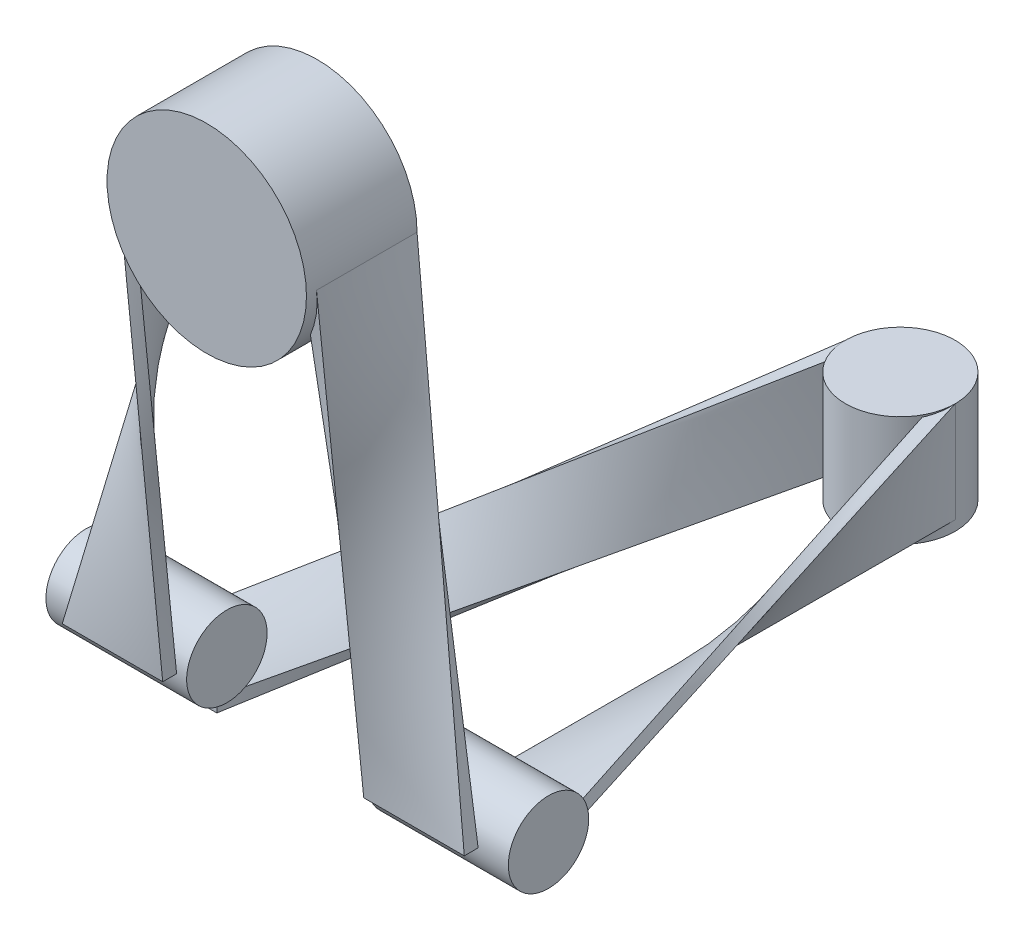
SolidWorks part; units mm, degrees
ref_plane "Front" through (0, 0, 0) normal (0, 0, 1) x (1, 0, 0)
ref_plane "Top" through (0, 0, 0) normal (0, 1, 0) x (1, 0, 0)
ref_plane "Right" through (0, 0, 0) normal (1, 0, 0) x (0, 0, -1)
sketch "Эскиз1" plane through (0, 0, 0) normal (0, 0, 1) x (1, 0, 0)
  circle A0 centre (0, 0) radius 9.9198
  dimension "D1" = 19.8396
extrude "Бобышка-Вытянуть1" add sketch "Эскиз1" along normal blind 11
ref_plane "Плоскость1" through (0, -46, 0) normal (0, 1, 0) x (1, 0, 0)
sketch "Эскиз3" plane through (0, -46, 0) normal (0, 1, 0) x (1, 0, 0)
  line L0 (0, 0) -> (0, 58)
  line L1 (0, -50) -> (0, 50) construction
  circle A0 centre (0, 58) radius 5.4635
  dimension "D1" = 10.9269
  dimension "D2" = 58
extrude "Бобышка-Вытянуть2" add sketch "Эскиз3" against normal blind 11 separate body contours A0 region at (3.754, -46, -54.246)
sketch "Эскиз4" plane through (0, 0, 0) normal (1, 0, 0) x (0, 0, -1)
  line L1 (0, 0) -> (0, -46)
  circle A0 centre (0, -46) radius 4
  dimension "D1" = 46
extrude "Бобышка-Вытянуть3" add sketch "Эскиз4" along normal blind 14 from offset 9 separate body contours A0
extrude "Бобышка-Вытянуть4" add sketch "Эскиз4<3>" against normal blind 14 from offset 9 separate body contours A0 region at (0, -48.7484, 2.7484) offset against normal yes
sketch "Эскиз4<3>" plane through (0, 0, 0) normal (1, 0, 0) x (0, 0, -1) same geometry as "Эскиз4"
sketch "Эскиз5" plane through (0, 0, 0) normal (0, 1, 0) x (1, 0, 0)
  line L0 (0, 0) -> (9.9198, 0) construction
  line L1 (-50, 0) -> (50, 0) construction
  line L2 (9.9198, -11) -> (9.9198, 0) construction
  line L5 (9.9198, -10) -> (8.5398, -10)
  line L6 (8.5398, -10) -> (8.5398, 0)
  line L7 (8.5398, 0) -> (9.9198, 0)
  line L9 (9.9198, -10) -> (9.9198, 0)
  point P9 (9.9198, -5)
ref_plane "Плоскость2" through (0, -46, 0) normal (0, 1, 0) x (1, 0, 0)
sketch "Эскиз6" plane through (0, -46, 0) normal (0, 1, 0) x (1, 0, 0)
  line L0 (0, -7) -> (15, -7) construction
  line L1 (0, -50) -> (0, 50) construction
  line L2 (15, -7) -> (15, -4) construction
  line L3 (9, -4) -> (23, -4) construction
  line L4 (0, -7) -> (-15, -7) construction
  line L5 (-15, -7) -> (-15, 0) construction
  line L7 (10, -4) -> (10, -5.38)
  line L8 (10, -5.38) -> (20, -5.38)
  line L9 (20, -5.38) -> (20, -4)
  line L11 (10, -4) -> (20, -4)
  dimension "D1" = 10
  dimension "D2" = 1.38
  dimension "D3" = 7
loft "По сечениям1" add section "Эскиз5" section "Эскиз6" connector at (9.9198, 0, 10) connector at (10, -46, 5.38)
ref_plane "Плоскость3" through (0, 0, 0) normal (0, 0, 1) x (1, 0, 0)
sketch "Эскиз7" plane through (0, 0, 0) normal (0, 0, 1) x (1, 0, 0)
  line L0 (0, 0) -> (0, -46) construction
  line L1 (50, -46) -> (-50, -46) construction
  line L2 (0, -50) -> (0, 50) construction
  line L3 (0, -46) -> (15, -46) construction
  line L4 (15, -46) -> (15, -50) construction
  line L6 (20, -50) -> (20, -51.38)
  line L7 (20, -51.38) -> (10, -51.38)
  line L8 (10, -51.38) -> (10, -50)
  line L10 (10, -50) -> (20, -50)
  dimension "D1" = 4
  dimension "D2" = 10
  dimension "D3" = 1.38
ref_plane "Плоскость4" through (0, 0, -58) normal (0, 0, 1) x (1, 0, 0)
sketch "Эскиз9" plane through (0, 0, -58) normal (0, 0, 1) x (1, 0, 0)
  line L0 (0, 0) -> (0, -46)
  line L1 (0, -56) -> (12.5746, -56) construction
  line L4 (0, 0) -> (0, -46) construction
  line L5 (50, -46) -> (-50, -46) construction
  line L6 (0, -46) -> (0, -56)
  line L8 (5.4635, -57) -> (5.4635, -46) construction
  line L9 (5.4635, -56) -> (5.4635, -46)
  line L10 (5.4635, -46) -> (4.0835, -46)
  line L11 (4.0835, -46) -> (4.0835, -56)
  line L12 (4.0835, -56) -> (5.4635, -56)
  dimension "D1" = 10
  dimension "D2" = 1.38
loft "По сечениям3" add section "Эскиз7" section "Эскиз9" connector at (20, -51.38, 0) connector at (5.4635, -46, -58)
mirror "Зеркальное отражение7" about plane through (0, 0, 0) normal (1, 0, 0) of bodies 107 105
